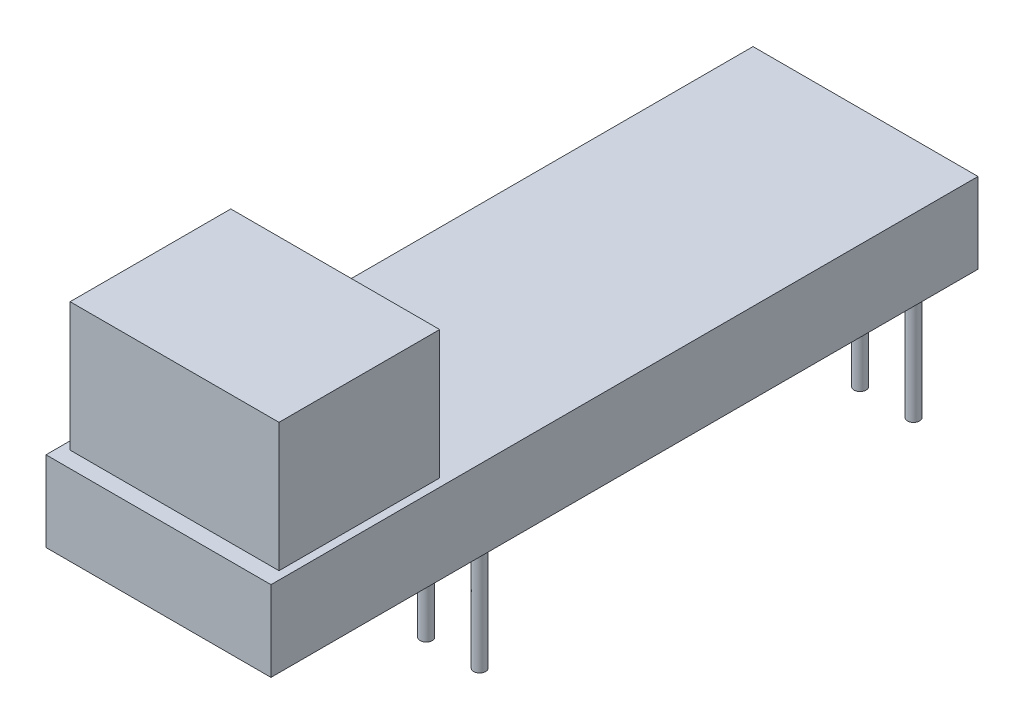
SolidWorks part; units mm, degrees
ref_plane "Front Plane" through (0, 0, 0) normal (0, 0, 1) x (1, 0, 0)
ref_plane "Top Plane" through (0, 0, 0) normal (0, 1, 0) x (1, 0, 0)
ref_plane "Right Plane" through (0, 0, 0) normal (1, 0, 0) x (0, 0, -1)
sketch "Sketch2" plane through (0, 0, 0) normal (0, 1, 0) x (1, 0, 0)
  line L1 (-7, 22) -> (7, 22)
  line L2 (-7, 22) -> (-7, -22)
  line L3 (-7, -22) -> (7, -22)
  line L4 (7, 22) -> (7, -22)
  line L5 (-7, 22) -> (7, -22) construction
  line L6 (-7, -22) -> (7, 22) construction
  point P0 (0, 0)
  dimension "D1" = 14
  dimension "D2" = 44
extrude "Boss-Extrude1" add sketch "Sketch2" along normal blind 5
sketch "Sketch3" plane through (0, 5, 0) normal (0, 1, 0) x (1, 0, 0)
  line L0 (0, -22) -> (0, 22) construction
  line L1 (-7, -22) -> (7, -22) construction
  line L2 (7, 22) -> (-7, 22) construction
  line L3 (-7, 0) -> (7, 0) construction
  line L4 (-7, 22) -> (-7, -22) construction
  line L5 (7, -22) -> (7, 22) construction
  line L7 (-6.5, -11) -> (6.5, -11)
  line L8 (-6.5, -11) -> (-6.5, -21)
  line L9 (-6.5, -21) -> (6.5, -21)
  line L10 (6.5, -11) -> (6.5, -21)
  line L11 (-6.5, -11) -> (6.5, -21) construction
  line L12 (-6.5, -21) -> (6.5, -11) construction
  point P12 (0, -16)
  dimension "D1" = 1
  dimension "D2" = 0.5
  dimension "D3" = 10
extrude "Boss-Extrude2" add sketch "Sketch3" along normal blind 8
sketch "Sketch4" plane through (0, 0, 0) normal (0, -1, 0) x (1, 0, 0)
  line L0 (7, 7) -> (-7, 7) construction
  line L1 (7, 22) -> (7, -22) construction
  line L2 (-7, -22) -> (-7, 22) construction
  line L3 (-7, 22) -> (7, 22) construction
  circle A0 centre (-5, 7) radius 0.375
  circle A1 centre (-1.67, 7) radius 0.375
  circle A2 centre (1.66, 7) radius 0.375
  circle A3 centre (4.99, 7) radius 0.375
  dimension "D2" = 0.75
  dimension "D3" = 2
  dimension "D5" = 5.33
  dimension "D1" = 15
  dimension "D4" = 4
extrude "Boss-Extrude3" add sketch "Sketch4" along normal blind 8
pattern_linear "LPattern1" count 2 spacing 27 along (0, 0, -1) of "Boss-Extrude3"
